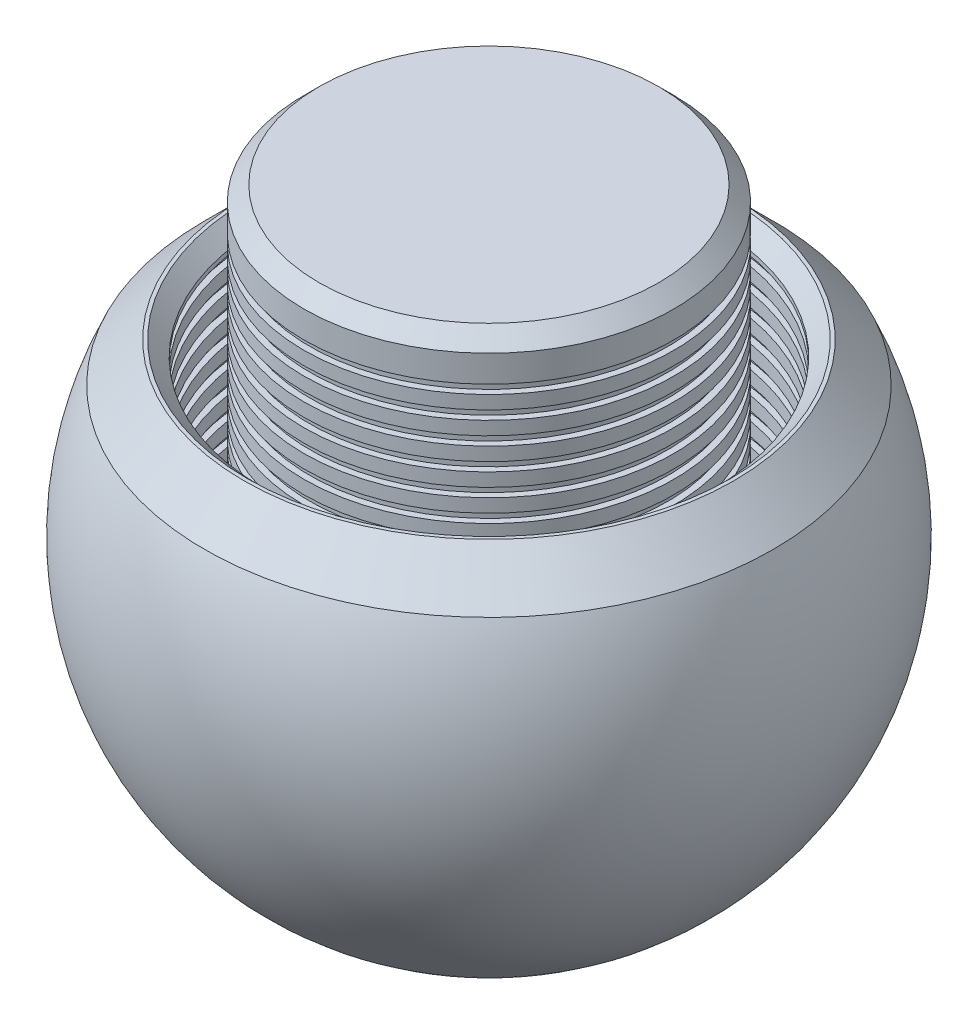
SolidWorks part; units mm, degrees
ref_plane "Front Plane" through (0, 0, 0) normal (0, 0, 1) x (1, 0, 0)
ref_plane "Top Plane" through (0, 0, 0) normal (0, 1, 0) x (1, 0, 0)
ref_plane "Right Plane" through (0, 0, 0) normal (1, 0, 0) x (0, 0, -1)
sketch "Sketch1" plane through (0, 0, 0) normal (0, 0, 1) x (1, 0, 0)
  line L0 (0, -1050.8) -> (0, -15) construction
  line L1 (0, -15) -> (0, 17)
  line L2 (0, 17) -> (10.5, 17)
  line L3 (10.5, 17) -> (10.5, -5)
  line L4 (10.5, -5) -> (12.5, -5)
  line L5 (12.5, -5) -> (12.5, 9.5)
  line L6 (12.5, 9.5) -> (14.6969, 9.5)
  line L7 (0, -15) -> (9.0139, -15)
  line L8 (0, -15) -> (0, 14.9124) construction
  arc A0 (9.0139, -15) -> (14.6969, 9.5) centre (0, 0) ccw
  dimension "D6" = 17.5
  dimension "D1" = 7.5
  dimension "D2" = 21
  dimension "D3" = 25
  dimension "D4" = 22
  dimension "D5" = 17
  dimension "D7" = 10
revolve "Revolve1" add sketch "Sketch1" angle 360 about L8
chamfer "Chamfer1" distance 1 angle 45 3 edges at (0, 9.5, -12.5) (0, 17, -10.5) (0, 9.5, -14.6969) first distance on face at (0, -5, -12.5) first distance on face at (0, 17, -10.5) first distance on face at (0, 9.5, -12.5)
other "Move Face1" flip direction yes face at (0, 16, 10.5) face at (0, 8.5, 12.5) offset 0.15 parameters "D1"=0.15
sketch "Sketch2" plane through (0, 0, 0) normal (0, 0, 1) x (1, 0, 0)
  line L0 (12.65, 8.65) -> (-12.65, 8.65) construction
  line L1 (-10.35, 16.15) -> (10.35, 16.15) construction
  line L2 (12.65, 8.65) -> (-12.65, 8.65) construction
  line L3 (-10.35, 16.15) -> (10.35, 16.15) construction
  line L4 (10.35, 16.15) -> (10.35, 8.65) construction
  line L5 (12.65, 7.5) -> (12.65, 16.7976) construction
  line L6 (11.5, 8.65) -> (11.5, 14.4) construction
  line L7 (10.35, 16.15) -> (12.65, 16.15) construction
  line L8 (0, 0) -> (0, 29.4171) construction
  line L9 (13, 14.65) -> (10, 14.65)
  line L10 (13, 14.65) -> (13, 14.15)
  line L11 (13, 14.15) -> (10, 14.15)
  line L12 (10, 14.65) -> (10, 14.15)
  line L13 (13, 14.65) -> (10, 14.15) construction
  line L14 (13, 14.15) -> (10, 14.65) construction
  point P9 (11.5, 16.15)
  dimension "D1" = 0.5
  dimension "D2" = 1.5
  dimension "D3" = 3
revolve "Cut-Revolve1" cut sketch "Sketch2" angle 360 about L8
pattern_linear "LPattern1" count 15 spacing 1.25 along (0, -1, 0) of "Cut-Revolve1"
